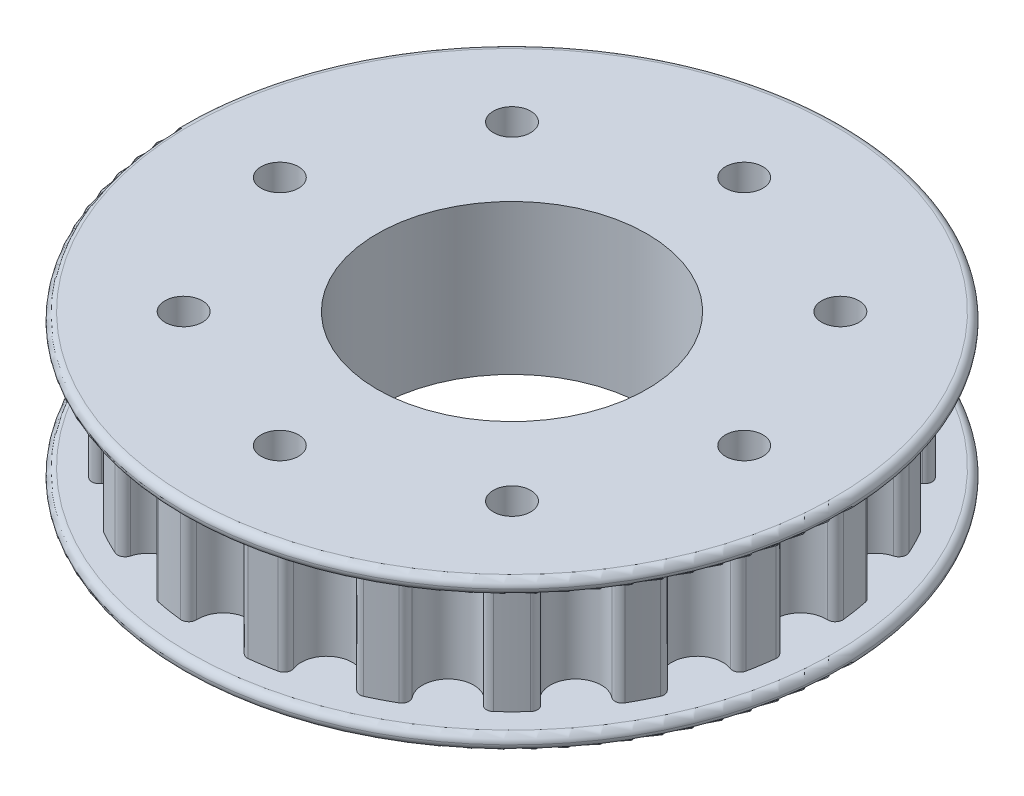
SolidWorks part; units mm, degrees
ref_plane "前视基准面" through (0, 0, 0) normal (0, 0, 1) x (1, 0, 0)
ref_plane "上视基准面" through (0, 0, 0) normal (0, 1, 0) x (1, 0, 0)
ref_plane "右视基准面" through (0, 0, 0) normal (1, 0, 0) x (0, 0, -1)
sketch "草图1" plane through (0, 0, 0) normal (0, 1, 0) x (1, 0, 0)
  line L0 (0, -0.7784) -> (0, 21.6766) construction
  arc A0 (-19.5985, 3.9875) -> (-19.8715, 2.2639) centre (0, 0) ccw
  arc A1 (-1.7079, 19.3499) -> (1.7079, 19.3499) centre (0, 19.2652) ccw
  arc A2 (2.2639, 19.8715) -> (1.7079, 19.3499) centre (2.2073, 19.3747) ccw
  arc A3 (-2.2639, 19.8715) -> (-1.7079, 19.3499) centre (-2.2073, 19.3747) cw
  arc A4 (8.2937, 18.1993) -> (7.6038, 17.8751) centre (8.0864, 17.7443) ccw
  arc A5 (4.3551, 18.9306) -> (7.6038, 17.8751) centre (5.9533, 18.3223) ccw
  arc A6 (3.9875, 19.5985) -> (4.3551, 18.9306) centre (3.8878, 19.1085) cw
  arc A7 (13.5117, 14.7457) -> (12.7553, 14.6505) centre (13.1739, 14.377) ccw
  arc A8 (9.9919, 16.6583) -> (12.7553, 14.6505) centre (11.3238, 15.5859) ccw
  arc A9 (9.8486, 17.407) -> (9.9919, 16.6583) centre (9.6024, 16.9718) cw
  arc A10 (17.407, 9.8486) -> (16.6583, 9.9919) centre (16.9718, 9.6024) ccw
  arc A11 (14.6505, 12.7553) -> (16.6583, 9.9919) centre (15.5859, 11.3238) ccw
  arc A12 (14.7457, 13.5117) -> (14.6505, 12.7553) centre (14.377, 13.1739) cw
  arc A13 (19.5985, 3.9875) -> (18.9306, 4.3551) centre (19.1085, 3.8878) ccw
  arc A14 (17.8751, 7.6038) -> (18.9306, 4.3551) centre (18.3223, 5.9533) ccw
  arc A15 (18.1993, 8.2937) -> (17.8751, 7.6038) centre (17.7443, 8.0864) cw
  arc A16 (19.8715, -2.2639) -> (19.3499, -1.7079) centre (19.3747, -2.2073) ccw
  arc A17 (19.3499, 1.7079) -> (19.3499, -1.7079) centre (19.2652, 0) ccw
  arc A18 (19.8715, 2.2639) -> (19.3499, 1.7079) centre (19.3747, 2.2073) cw
  arc A19 (18.1993, -8.2937) -> (17.8751, -7.6038) centre (17.7443, -8.0864) ccw
  arc A20 (18.9306, -4.3551) -> (17.8751, -7.6038) centre (18.3223, -5.9533) ccw
  arc A21 (19.5985, -3.9875) -> (18.9306, -4.3551) centre (19.1085, -3.8878) cw
  arc A22 (14.7457, -13.5117) -> (14.6505, -12.7553) centre (14.377, -13.1739) ccw
  arc A23 (16.6583, -9.9919) -> (14.6505, -12.7553) centre (15.5859, -11.3238) ccw
  arc A24 (17.407, -9.8486) -> (16.6583, -9.9919) centre (16.9718, -9.6024) cw
  arc A25 (9.8486, -17.407) -> (9.9919, -16.6583) centre (9.6024, -16.9718) ccw
  arc A26 (12.7553, -14.6505) -> (9.9919, -16.6583) centre (11.3238, -15.5859) ccw
  arc A27 (13.5117, -14.7457) -> (12.7553, -14.6505) centre (13.1739, -14.377) cw
  arc A28 (3.9875, -19.5985) -> (4.3551, -18.9306) centre (3.8878, -19.1085) ccw
  arc A29 (7.6038, -17.8751) -> (4.3551, -18.9306) centre (5.9533, -18.3223) ccw
  arc A30 (8.2937, -18.1993) -> (7.6038, -17.8751) centre (8.0864, -17.7443) cw
  arc A31 (-2.2639, -19.8715) -> (-1.7079, -19.3499) centre (-2.2073, -19.3747) ccw
  arc A32 (1.7079, -19.3499) -> (-1.7079, -19.3499) centre (0, -19.2652) ccw
  arc A33 (2.2639, -19.8715) -> (1.7079, -19.3499) centre (2.2073, -19.3747) cw
  arc A34 (-8.2937, -18.1993) -> (-7.6038, -17.8751) centre (-8.0864, -17.7443) ccw
  arc A35 (-4.3551, -18.9306) -> (-7.6038, -17.8751) centre (-5.9533, -18.3223) ccw
  arc A36 (-3.9875, -19.5985) -> (-4.3551, -18.9306) centre (-3.8878, -19.1085) cw
  arc A37 (-13.5117, -14.7457) -> (-12.7553, -14.6505) centre (-13.1739, -14.377) ccw
  arc A38 (-9.9919, -16.6583) -> (-12.7553, -14.6505) centre (-11.3238, -15.5859) ccw
  arc A39 (-9.8486, -17.407) -> (-9.9919, -16.6583) centre (-9.6024, -16.9718) cw
  arc A40 (-17.407, -9.8486) -> (-16.6583, -9.9919) centre (-16.9718, -9.6024) ccw
  arc A41 (-14.6505, -12.7553) -> (-16.6583, -9.9919) centre (-15.5859, -11.3238) ccw
  arc A42 (-14.7457, -13.5117) -> (-14.6505, -12.7553) centre (-14.377, -13.1739) cw
  arc A43 (-19.5985, -3.9875) -> (-18.9306, -4.3551) centre (-19.1085, -3.8878) ccw
  arc A44 (-17.8751, -7.6038) -> (-18.9306, -4.3551) centre (-18.3223, -5.9533) ccw
  arc A45 (-18.1993, -8.2937) -> (-17.8751, -7.6038) centre (-17.7443, -8.0864) cw
  arc A46 (-19.8715, 2.2639) -> (-19.3499, 1.7079) centre (-19.3747, 2.2073) ccw
  arc A47 (-19.3499, -1.7079) -> (-19.3499, 1.7079) centre (-19.2652, 0) ccw
  arc A48 (-19.8715, -2.2639) -> (-19.3499, -1.7079) centre (-19.3747, -2.2073) cw
  arc A49 (-18.1993, 8.2937) -> (-17.8751, 7.6038) centre (-17.7443, 8.0864) ccw
  arc A50 (-18.9306, 4.3551) -> (-17.8751, 7.6038) centre (-18.3223, 5.9533) ccw
  arc A51 (-19.5985, 3.9875) -> (-18.9306, 4.3551) centre (-19.1085, 3.8878) cw
  arc A52 (-14.7457, 13.5117) -> (-14.6505, 12.7553) centre (-14.377, 13.1739) ccw
  arc A53 (-16.6583, 9.9919) -> (-14.6505, 12.7553) centre (-15.5859, 11.3238) ccw
  arc A54 (-17.407, 9.8486) -> (-16.6583, 9.9919) centre (-16.9718, 9.6024) cw
  arc A55 (-9.8486, 17.407) -> (-9.9919, 16.6583) centre (-9.6024, 16.9718) ccw
  arc A56 (-12.7553, 14.6505) -> (-9.9919, 16.6583) centre (-11.3238, 15.5859) ccw
  arc A57 (-13.5117, 14.7457) -> (-12.7553, 14.6505) centre (-13.1739, 14.377) cw
  arc A58 (-3.9875, 19.5985) -> (-4.3551, 18.9306) centre (-3.8878, 19.1085) ccw
  arc A59 (-7.6038, 17.8751) -> (-4.3551, 18.9306) centre (-5.9533, 18.3223) ccw
  arc A60 (-8.2937, 18.1993) -> (-7.6038, 17.8751) centre (-8.0864, 17.7443) cw
  arc A61 (-19.8715, -2.2639) -> (-19.5985, -3.9875) centre (0, 0) ccw
  arc A62 (-18.1993, -8.2937) -> (-17.407, -9.8486) centre (0, 0) ccw
  arc A63 (-14.7457, -13.5117) -> (-13.5117, -14.7457) centre (0, 0) ccw
  arc A64 (-9.8486, -17.407) -> (-8.2937, -18.1993) centre (0, 0) ccw
  arc A65 (-3.9875, -19.5985) -> (-2.2639, -19.8715) centre (0, 0) ccw
  arc A66 (2.2639, -19.8715) -> (3.9875, -19.5985) centre (0, 0) ccw
  arc A67 (8.2937, -18.1993) -> (9.8486, -17.407) centre (0, 0) ccw
  arc A68 (13.5117, -14.7457) -> (14.7457, -13.5117) centre (0, 0) ccw
  arc A69 (17.407, -9.8486) -> (18.1993, -8.2937) centre (0, 0) ccw
  arc A70 (19.5985, -3.9875) -> (19.8715, -2.2639) centre (0, 0) ccw
  arc A71 (19.8715, 2.2639) -> (19.5985, 3.9875) centre (0, 0) ccw
  arc A72 (18.1993, 8.2937) -> (17.407, 9.8486) centre (0, 0) ccw
  arc A73 (14.7457, 13.5117) -> (13.5117, 14.7457) centre (0, 0) ccw
  arc A74 (9.8486, 17.407) -> (8.2937, 18.1993) centre (0, 0) ccw
  arc A75 (3.9875, 19.5985) -> (2.2639, 19.8715) centre (0, 0) ccw
  arc A76 (-2.2639, 19.8715) -> (-3.9875, 19.5985) centre (0, 0) ccw
  arc A77 (-8.2937, 18.1993) -> (-9.8486, 17.407) centre (0, 0) ccw
  arc A78 (-13.5117, 14.7457) -> (-14.7457, 13.5117) centre (0, 0) ccw
  arc A79 (-17.407, 9.8486) -> (-18.1993, 8.2937) centre (0, 0) ccw
  point P147 (0, 0)
  dimension "D1" = 40
  dimension "D2" = 0.5
  dimension "D3" = 0.5
  dimension "D4" = 1.71
  dimension "D5" = 20
extrude "凸台-拉伸1" add sketch "草图1" along normal blind 8
sketch "草图2" plane through (0, 0, 0) normal (0, 1, 0) x (1, 0, 0)
  circle A0 centre (0, 0) radius 22
  dimension "D1" = 44
extrude "凸台-拉伸2" add sketch "草图2" against normal blind 1
fillet "圆角1" radius 0.5 2 edges at (0, 0, 22) (0, -1, 22)
sketch "草图3" plane through (0, 8, 0) normal (0, 1, 0) x (1, 0, 0)
  circle A0 centre (0, 0) radius 22
extrude "凸台-拉伸3" add sketch "草图3" along normal blind 1
fillet "圆角2" radius 0.5 2 edges at (0, 8, 22) (0, 9, 22)
sketch "草图7" plane through (0, 9, 0) normal (0, 1, 0) x (1, 0, 0)
  circle A0 centre (0, 0) radius 15.5 construction
  circle A1 centre (0, 15.5) radius 1.5
  circle A2 centre (10.9602, 10.9602) radius 1.5
  circle A3 centre (15.5, 0) radius 1.5
  circle A4 centre (10.9602, -10.9602) radius 1.5
  circle A5 centre (0, -15.5) radius 1.5
  circle A6 centre (-10.9602, -10.9602) radius 1.5
  circle A7 centre (-15.5, 0) radius 1.5
  circle A8 centre (-10.9602, 10.9602) radius 1.5
  point P21 (0, 0)
  dimension "D1" = 31
  dimension "D2" = 3
  dimension "D3" = 8
hole_wizard "M3 螺纹孔的螺纹孔钻头1" positions "3D草图2" profile "草图8" hole size "M3" standard "GB" end condition through all
sketch3d "3D草图2"
  point P0 (-10.9602, 9, -10.9602)
  point P3 (0, 9, -15.5)
  point P6 (10.9602, 9, -10.9602)
  point P9 (15.5, 9, 0)
  point P12 (10.9602, 9, 10.9602)
  point P15 (0, 9, 15.5)
  point P18 (-10.9602, 9, 10.9602)
  point P21 (-15.5, 9, 0)
sketch "草图8" plane through (-10.9602, 9, -10.9602) normal (1, 0, 0) x (0, 0, 1)
  line L0 (0, 0) -> (0, 10)
  line L1 (0, 10) -> (1.25, 10)
  line L2 (1.25, 10) -> (1.25, 0)
  line L5 (1.25, 0) -> (0, 0)
  line L11 (0, -6.35) -> (0, 107.95) construction
  dimension "通孔孔直径" = 2.5
  dimension "通孔孔深度" = 10
sketch "草图9" plane through (0, 9, 0) normal (0, 1, 0) x (1, 0, 0)
  circle A0 centre (0, 0) radius 9
  dimension "D1" = 18
extrude "切除-拉伸2" cut sketch "草图9" against normal through all
